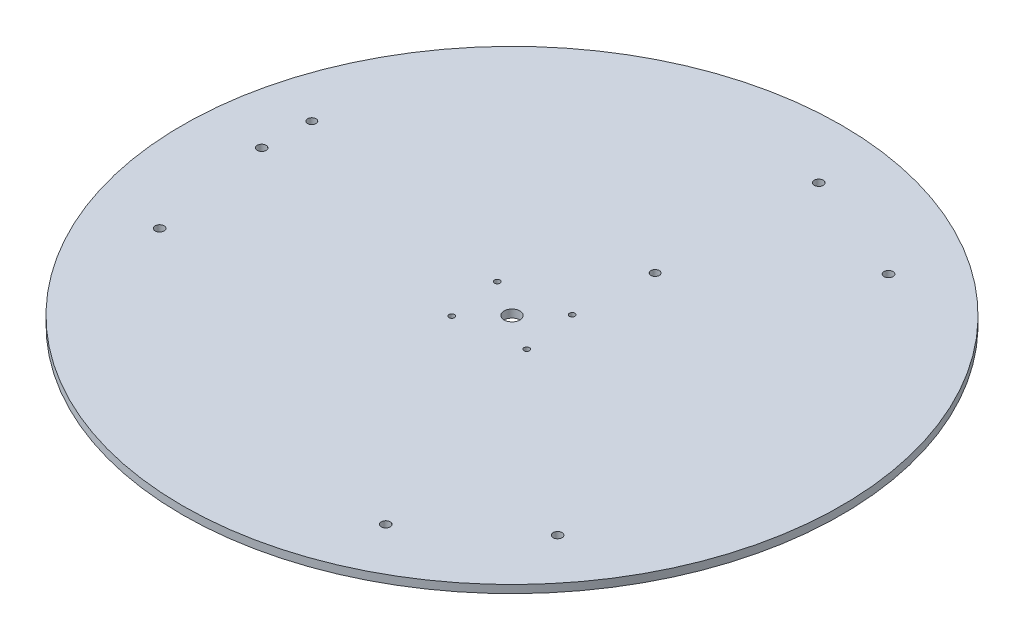
SolidWorks part; units mm, degrees
ref_plane "Front Plane" through (0, 0, 0) normal (0, 0, 1) x (1, 0, 0)
ref_plane "Top Plane" through (0, 0, 0) normal (0, 1, 0) x (1, 0, 0)
ref_plane "Right Plane" through (0, 0, 0) normal (1, 0, 0) x (0, 0, -1)
sketch "Sketch2" plane through (0, 0, 0) normal (0, 1, 0) x (1, 0, 0)
  circle A0 centre (0, 0) radius 125
  dimension "D1" = 250
extrude "Boss-Extrude1" add sketch "Sketch2" along normal blind 3
sketch "Sketch3" plane through (0, 3, 0) normal (0, 1, 0) x (1, 0, 0)
  line L4 (74.6446, 100.2656) -> (65.4599, 76.5843) construction
  line L5 (0, 0) -> (43.5629, 112.3204) construction
  line L6 (74.6446, 100.2656) -> (12.4813, 124.3753) construction
  line L7 (12.4813, 124.3753) -> (3.2966, 100.6941) construction
  line L8 (65.4599, 76.5843) -> (3.2966, 100.6941) construction
  circle A0 centre (0, 0) radius 125 construction
  circle A7 centre (57.8244, 84.9944) radius 1.7
  circle A8 centre (14.6061, 101.7564) radius 1.7
  circle A9 centre (44.6952, -92.5746) radius 1.7
  circle A10 centre (80.8206, -63.5274) radius 1.7
  circle A11 centre (-102.5195, 7.5802) radius 1.7
  circle A12 centre (-95.4267, -38.229) radius 1.7
  point P22 (0, 0)
  point P23 (0.4661, 0.2121)
  dimension "D2" = 3.4
  dimension "D1" = 25.4
  dimension "D3" = 5.08
  dimension "D5" = 66.675
  dimension "D6" = 3
  dimension "D4" = 10.16
extrude "Cut-Extrude1" cut sketch "Sketch3" against normal blind 26 and the other way blind 62
sketch "Sketch4" plane through (0, 3, 0) normal (0, 1, 0) x (1, 0, 0)
  circle A0 centre (0, 0) radius 3
  dimension "D1" = 6
extrude "Cut-Extrude2" cut sketch "Sketch4" against normal blind 33 and the other way blind 55
sketch "Sketch5" plane through (0, 0, 0) normal (0, -1, 0) x (1, 0, 0)
  circle A0 centre (-101.7781, -25.8548) radius 1.6
  circle A1 centre (13.2168, -41.0922) radius 1.6
  dimension "D1" = 3.2
  dimension "D2" = 3.2
extrude "Cut-Extrude3" cut sketch "Sketch5" against normal through all
sketch "Sketch6" plane through (0, 3, 0) normal (0, 1, 0) x (1, 0, 0)
  circle A0 centre (11.1984, 11.6251) radius 1.05
  circle A1 centre (13.8892, -8.3009) radius 1.05
  circle A2 centre (-11.1984, -11.6251) radius 1.05
  circle A3 centre (-13.8892, 8.3009) radius 1.05
extrude "Cut-Extrude4" cut sketch "Sketch6" against normal up to next
